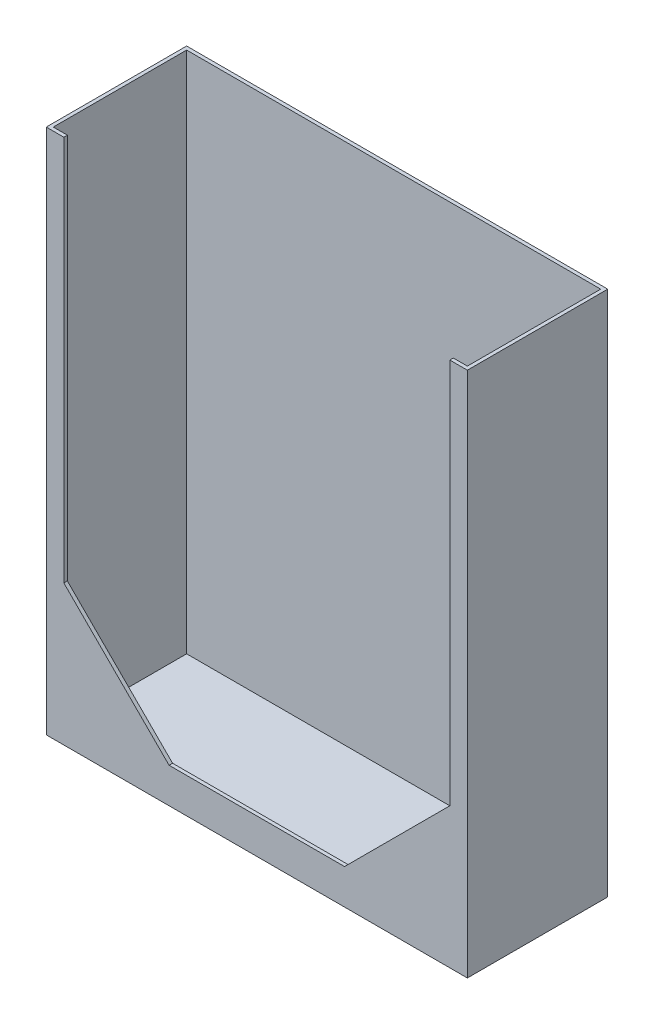
SolidWorks part; units mm, degrees
ref_plane "Front Plane" through (0, 0, 0) normal (0, 0, 1) x (1, 0, 0)
ref_plane "Top Plane" through (0, 0, 0) normal (0, 1, 0) x (1, 0, 0)
ref_plane "Right Plane" through (0, 0, 0) normal (1, 0, 0) x (0, 0, -1)
sketch "Sketch1" plane through (0, 0, 0) normal (0, 1, 0) x (1, 0, 0)
  line L0 (-152.4, 50.8) -> (152.4, -50.8) construction
  line L1 (-152.4, 50.8) -> (152.4, 50.8)
  line L2 (-152.4, 50.8) -> (-152.4, -50.8)
  line L3 (-152.4, -50.8) -> (152.4, -50.8)
  line L4 (152.4, 50.8) -> (152.4, -50.8)
  dimension "D1" = 304.8
  dimension "D2" = 101.6
extrude "Boss-Extrude1" add sketch "Sketch1" along normal mid plane 381
shell "Shell1" thickness 2.54 removed face at (0, 190.5, 0)
sketch "Sketch2" plane through (0, 0, 50.8) normal (0, 0, 1) x (1, 0, 0)
  line L0 (-152.4, 190.5) -> (-152.4, -190.5) construction
  line L1 (-139.7, 190.5) -> (139.7, 190.5)
  line L2 (-139.7, 190.5) -> (-139.7, -88.9)
  line L3 (-63.5, -165.1) -> (63.5, -165.1)
  line L4 (139.7, 190.5) -> (139.7, -88.9)
  line L5 (-139.7, 0) -> (0, 0) construction
  line L6 (0, 0) -> (139.7, 0) construction
  line L7 (-152.4, 190.5) -> (152.4, 190.5) construction
  line L8 (-152.4, -190.5) -> (152.4, -190.5) construction
  line L9 (-139.7, -88.9) -> (-63.5, -165.1)
  line L10 (63.5, -165.1) -> (139.7, -88.9)
  dimension "D1" = 12.7
  dimension "D2" = 25.4
  dimension "D3" = 45
  dimension "D4" = 76.2
extrude "Cut-Extrude1" cut sketch "Sketch2" against normal up to next
